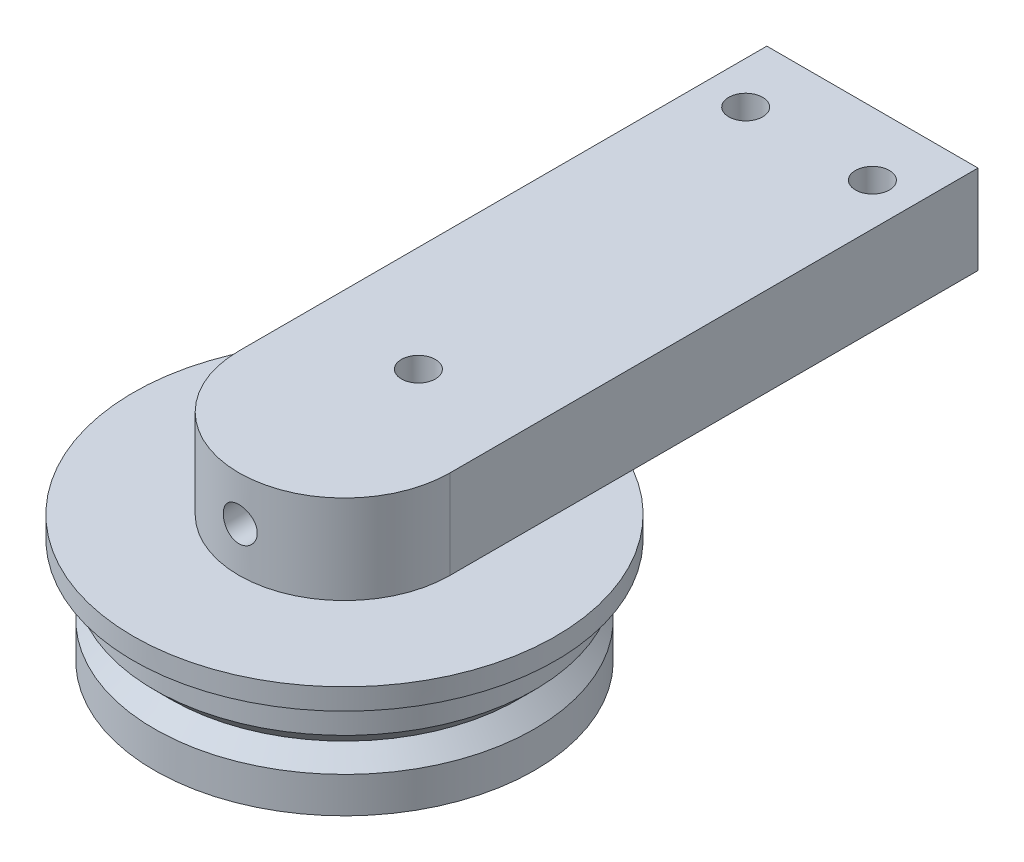
SolidWorks part; units mm, degrees
material "6061 Alloy"
ref_plane "Front Plane" through (0, 0, 0) normal (0, 0, 1) x (1, 0, 0)
ref_plane "Top Plane" through (0, 0, 0) normal (0, 1, 0) x (1, 0, 0)
ref_plane "Right Plane" through (0, 0, 0) normal (1, 0, 0) x (0, 0, -1)
sketch "Sketch1" plane through (0, 0, 0) normal (0, 1, 0) x (1, 0, 0)
  line L0 (-15.875, 0) -> (-15.875, 79.375)
  line L1 (-15.875, 79.375) -> (15.875, 79.375)
  line L2 (15.875, 79.375) -> (15.875, 0)
  arc A0 (-15.875, 0) -> (15.875, 0) centre (0, 0) ccw
  point P14 (0, -15.875)
  dimension "D1" = 95.25
  dimension "D3" = 31.75
extrude "Boss-Extrude1" add sketch "Sketch1" along normal blind 13.3524
sketch "Sketch4" plane through (0, 0, 0) normal (0, -1, 0) x (1, 0, 0)
  circle A0 centre (0, 0) radius 28.575
  dimension "D1" = 57.15
extrude "Boss-Extrude2" add sketch "Sketch4" along normal up to surface (19.05 mm away)
ref_axis "Axis1" through (0, -19.05, 0) along (0, 1, 0)
sketch "Sketch22" plane through (0, 0, 0) normal (0, 0, 1) x (1, 0, 0)
  line L0 (28.575, -8.5725) -> (26.035, -11.1125)
  line L1 (26.035, -11.1125) -> (28.575, -13.6525)
  line L2 (28.575, -8.5725) -> (28.575, -13.6525) construction
  line L3 (28.575, -19.05) -> (28.575, 0) construction
  line L5 (28.575, -8.5725) -> (28.575, -13.6525)
  line L7 (26.035, -11.1125) -> (28.575, -11.1125) construction
  line L8 (28.575, 0) -> (-28.575, 0) construction
  dimension "D1" = 90
  dimension "D2" = 11.1125
  dimension "D3" = 5.08
sketch "Sketch2" plane through (0, 13.3524, 0) normal (0, 1, 0) x (1, 0, 0)
  circle A0 centre (0, 0) radius 6.35
sketch "Sketch5" plane through (0, 0, 0) normal (0, -1, 0) x (1, 0, 0)
  circle A0 centre (0, 0) radius 31.75
  circle A1 centre (0, 0) radius 28.575
  dimension "D1" = 57.15
  dimension "D2" = 63.5
extrude "Boss-Extrude3" add sketch "Sketch5" along normal blind 3.175
hole_wizard "1/4-20 Tapped Hole1" positions "Sketch13" profile "Sketch15" tap size "1/4-20" standard "ANSI Inch" end condition through all
sketch "Sketch13" plane through (0, 0, -79.375) normal (0, 0, -1) x (-1, 0, 0)
  line L0 (-15.875, 6.6762) -> (15.875, 6.6762) construction
  line L1 (-15.875, 13.3524) -> (-15.875, 0) construction
  line L2 (15.875, 13.3524) -> (15.875, 0) construction
  line L4 (0, 0) -> (0, 13.3524) construction
  line L5 (-15.875, 13.3524) -> (15.875, 13.3524) construction
  point P0 (0, 6.6762)
sketch "Sketch15" plane through (0, 6.6762, -79.375) normal (1, 0, 0) x (0, 1, 0)
  line L0 (0, 0) -> (0, 111.125)
  line L1 (0, 111.125) -> (2.5527, 111.125)
  line L2 (2.5527, 111.125) -> (2.5527, 0)
  line L5 (2.5527, 0) -> (0, 0)
  line L11 (0, -6.35) -> (0, 107.95) construction
  dimension "Thru Tap Drill Dia." = 5.1054
  dimension "Thru Tap Drill Depth" = 111.125
cosmetic thread "Hole Thread7" parameters "D2"=6.35
hole_wizard "1/4-20 Tapped Hole2" positions "Sketch20" profile "Sketch21" tap size "1/4-20" standard "ANSI Inch"
sketch "Sketch20" plane through (0, 13.3524, 0) normal (0, 1, 0) x (1, 0, 0)
  line L0 (0, 79.375) -> (0, 0) construction
  line L1 (15.875, 79.375) -> (-15.875, 79.375) construction
  point P0 (-9.525, 69.85)
  point P2 (9.525, 69.85)
  point P5 (0, 11.1125)
  dimension "D2" = 68.2625
sketch "Sketch21" plane through (-9.525, 13.3524, -69.85) normal (1, 0, 0) x (0, 0, 1)
  line L0 (0, 0) -> (0, 119.8038)
  line L1 (0, 119.8038) -> (2.5527, 118.27)
  line L2 (2.5527, 118.27) -> (2.5527, 0)
  line L5 (2.5527, 0) -> (0, 0)
  line L10 (0, 119.8038) -> (-2.5527, 118.27) construction
  line L11 (0, -6.35) -> (0, 107.95) construction
  dimension "Tap Drill Dia." = 5.1054
  dimension "Tap Drill Depth" = 118.27
  dimension "Drill Angle" = 118
cosmetic thread "Hole Thread8" parameters "D1"=95.25, "D2"=6.35
cosmetic thread "Hole Thread9" parameters "D1"=95.25, "D2"=6.35
cosmetic thread "Hole Thread10" parameters "D1"=95.25, "D2"=6.35
revolve "Cut-Revolve2" cut sketch "Sketch22" angle 360 about axis through (0, -19.05, 0) along (0, 1, 0)
extrude "Boss-Extrude6" add sketch "Sketch2" against normal offset from surface (37.9904 mm away) 5.588 up to face at (2.5527, -19.05, -11.1125) offset beyond the face yes
ref_axis "Axis2" through (0, -24.638, 0) along (0, 1, 0)
sketch "Sketch23" plane through (0, 0, 0) normal (1, 0, 0) x (0, 0, -1)
  line L1 (-6.35, -15.8893) -> (-5.9436, -15.8893)
  line L2 (-6.35, -15.8893) -> (-6.35, -16.8799)
  line L3 (-6.35, -16.8799) -> (-5.9436, -16.8799)
  line L4 (-5.9436, -15.8893) -> (-5.9436, -16.8799)
  line L5 (-41.9752, -15.8893) -> (-40.1854, -15.8893) construction
  line L6 (-6.35, -19.05) -> (-6.35, -24.638) construction
  dimension "D1" = 0.9906
  dimension "D2" = 0.4064
revolve "Cut-Revolve4" cut sketch "Sketch23" angle 360 about axis through (0, -24.638, 0) along (0, 1, 0)
